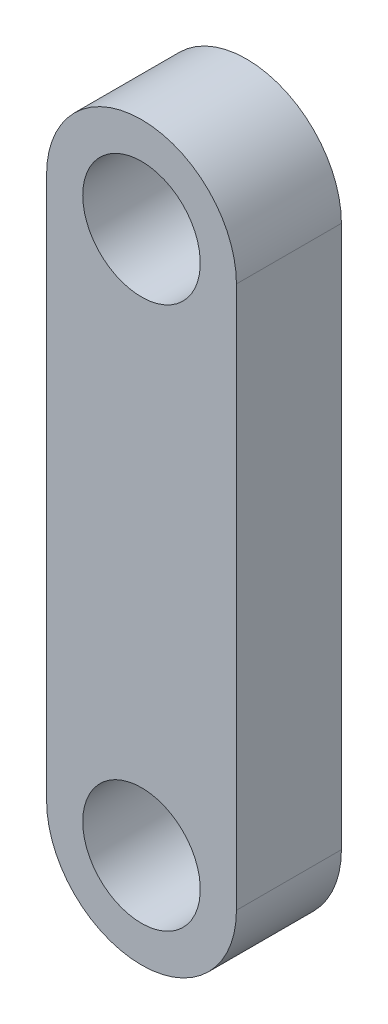
SolidWorks part; units mm, degrees
ref_plane "Front Plane" through (0, 0, 0) normal (0, 0, 1) x (1, 0, 0)
ref_plane "Top Plane" through (0, 0, 0) normal (0, 1, 0) x (1, 0, 0)
ref_plane "Right Plane" through (0, 0, 0) normal (1, 0, 0) x (0, 0, -1)
sketch "Sketch1" plane through (0, 0, 0) normal (0, 0, 1) x (1, 0, 0)
  line L1 (-5.425, 0) -> (-5.425, -31)
  line L2 (5.425, 0) -> (5.425, -31)
  circle A0 centre (0, 0) radius 3.3583
  circle A1 centre (0, -31) radius 3.3583
  arc A4 (-5.425, 0) -> (5.425, 0) centre (0, 0) cw
  arc A6 (-5.425, -31) -> (5.425, -31) centre (0, -31) ccw
  dimension "D1" = 31
extrude "Boss-Extrude1" add sketch "Sketch1" along normal blind 6 contours L1 A6 L2 A4
extrude "Cut-Extrude1" cut sketch "Sketch1<3>" along normal blind 16 contours A1 | A0 region at (0, -31, 0)
sketch "Sketch1<3>" plane through (0, 0, 0) normal (0, 0, 1) x (1, 0, 0) same geometry as "Sketch1"
